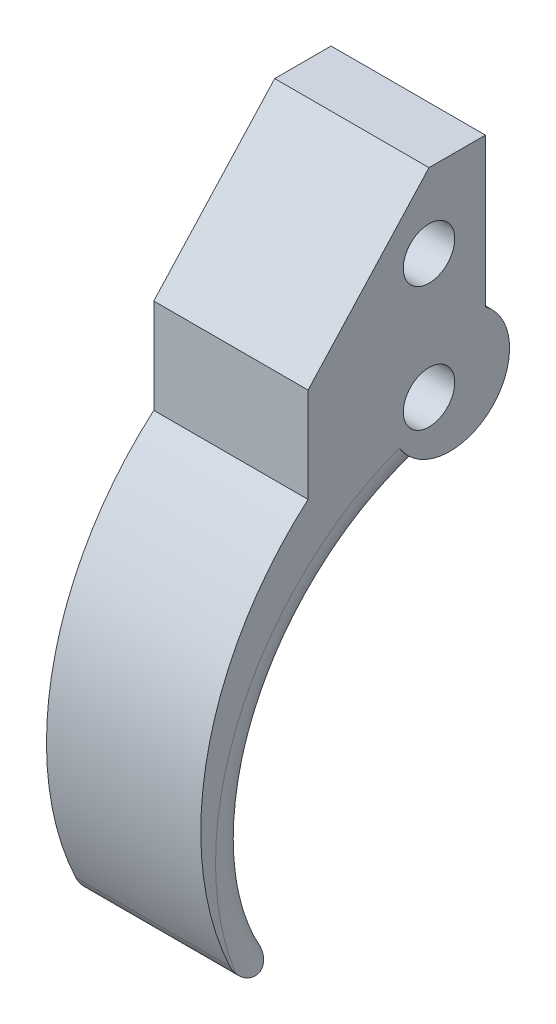
SolidWorks part; units mm, degrees
material "1060 Alloy"
ref_plane "Front Plane" through (0, 0, 0) normal (0, 0, 1) x (1, 0, 0)
ref_plane "Top Plane" through (0, 0, 0) normal (0, 1, 0) x (1, 0, 0)
ref_plane "Right Plane" through (0, 0, 0) normal (1, 0, 0) x (0, 0, -1)
sketch "Sketch1" plane through (0, 0, 0) normal (1, 0, 0) x (0, 0, -1)
  line L0 (-8.0719, -24.2294) -> (-10.2017, -25.3935)
  line L1 (-6.8972, -1.3882) -> (-6.8972, 4.2243)
  line L2 (-6.8972, 4.2243) -> (0.2683, 12.0555)
  line L3 (0.2683, 12.0555) -> (3.6098, 12.0555)
  line L4 (3.6098, 12.0555) -> (3.6098, 3.2454)
  circle A0 centre (0.2683, 0.2748) radius 1.524
  arc A1 (3.6098, 3.2454) -> (2.0435, -3.0849) centre (1.5095, 0.4061) cw
  arc A2 (2.0435, -3.0849) -> (-8.0719, -24.2294) centre (4.6029, -17.3011) ccw
  arc A3 (-10.2017, -25.3935) -> (-6.8972, -1.3882) centre (5.0726, -15.266) cw
  circle A4 centre (0.2683, 7.6504) radius 1.524
extrude "Boss-Extrude1" add sketch "Sketch1" along normal blind 9.144
fillet "Fillet1" radius 2.54 3 edges at (4.572, -25.3935, 10.2017) (0, -11.0674, 8.4275) (9.144, -11.0674, 8.4275)
